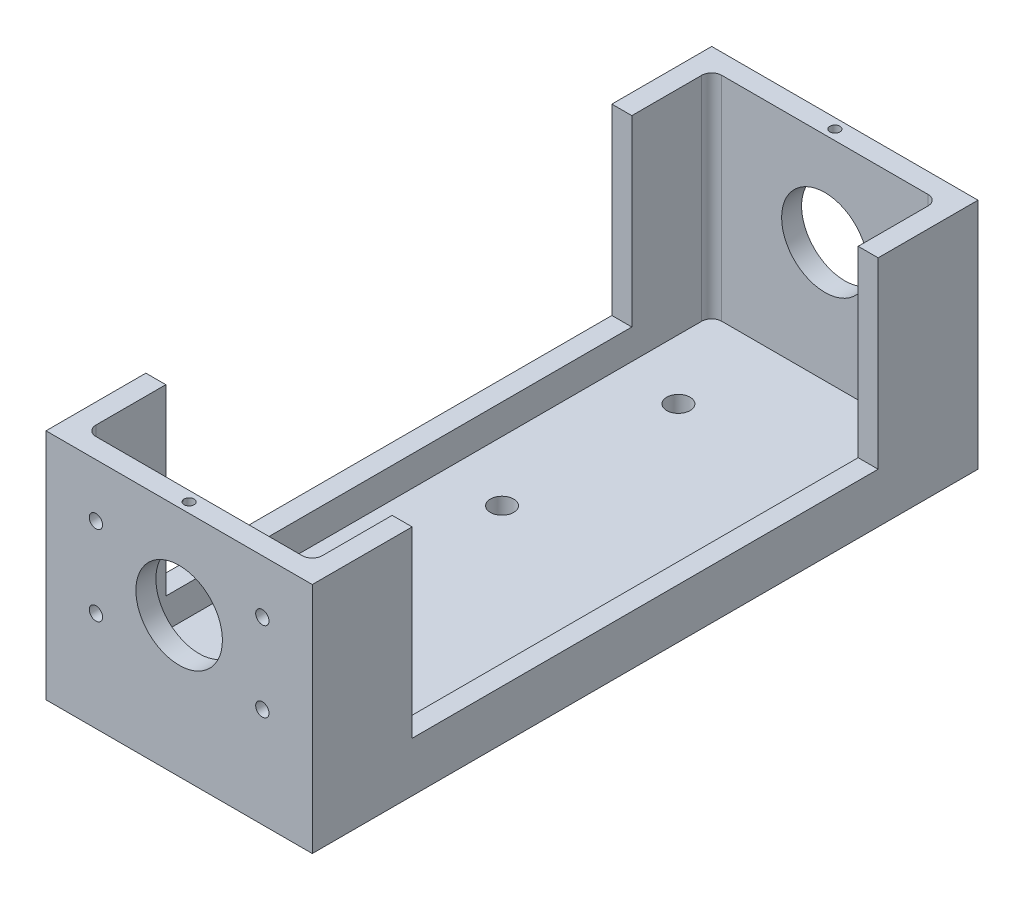
SolidWorks part; units mm, degrees
ref_plane "前视基准面" through (0, 0, 0) normal (0, 0, 1) x (1, 0, 0)
ref_plane "上视基准面" through (0, 0, 0) normal (0, 1, 0) x (1, 0, 0)
ref_plane "右视基准面" through (0, 0, 0) normal (1, 0, 0) x (0, 0, -1)
sketch "草图1" plane through (0, 0, 0) normal (0, 0, 1) x (1, 0, 0)
  line L1 (-40, -35) -> (40, -35)
  line L2 (-40, -35) -> (-40, 35)
  line L3 (-40, 35) -> (40, 35)
  line L4 (40, -35) -> (40, 35)
  line L5 (-40, -35) -> (40, 35) construction
  line L6 (-40, 35) -> (40, -35) construction
  point P0 (0, 0)
  dimension "D1" = 80
  dimension "D2" = 70
extrude "凸台-拉伸1" add sketch "草图1" against normal blind 200
sketch "草图2" plane through (0, 35, 0) normal (0, 1, 0) x (1, 0, 0)
  line L0 (-34, 191) -> (-34, 9)
  line L1 (-31, 6) -> (31, 6)
  line L2 (34, 9) -> (34, 191)
  line L3 (31, 194) -> (-31, 194)
  line L4 (-40, 0) -> (40, 0)
  line L5 (40, 0) -> (40, 200)
  line L6 (40, 200) -> (-40, 200)
  line L7 (-40, 200) -> (-40, 0)
  line L8 (-40, 0) -> (40, 0)
  line L9 (40, 0) -> (40, 200)
  line L10 (40, 200) -> (-40, 200)
  line L11 (-40, 200) -> (-40, 0)
  line L12 (-34, 6) -> (34, 6) construction
  line L13 (34, 6) -> (34, 194) construction
  line L14 (-34, 194) -> (-34, 6) construction
  line L15 (34, 194) -> (-34, 194) construction
  arc A0 (31, 6) -> (34, 9) centre (31, 9) ccw
  arc A1 (-34, 9) -> (-31, 6) centre (-31, 9) ccw
  arc A2 (34, 191) -> (31, 194) centre (31, 191) ccw
  arc A3 (-34, 191) -> (-31, 194) centre (-31, 191) cw
  dimension "D3" = 3
  dimension "D1" = 0
  dimension "D2" = 6
extrude "切除-拉伸1" cut sketch "草图2" against normal blind 64 contours A3 L0 A1 L1 A0 L2 A2 L3 region at (0, 35, -100)
sketch "草图3" plane through (0, 0, 0) normal (0, 0, 1) x (1, 0, 0)
  line L0 (0, 0) -> (0, 37.0041) construction
  line L1 (-40, -29) -> (40, -29) construction
  line L2 (-40, 35) -> (-40, -35) construction
  line L3 (40, -35) -> (40, 35) construction
  line L4 (-40, -35) -> (40, -35) construction
  line L5 (40, 35) -> (-40, 35) construction
  line L6 (-34, -29) -> (40, -29) construction
  line L9 (0, 7) -> (0, 35) construction
  line L10 (-26, 7) -> (26, 7) construction
  circle A0 centre (-26, 7) radius 3.5 construction
  circle A1 centre (0, 7) radius 13
  circle A2 centre (26, 7) radius 3.5 construction
  dimension "D2" = 7
  dimension "D3" = 26
  dimension "D4" = 7
  dimension "D1" = 6
  dimension "D5" = 28
  dimension "D6" = 26
  dimension "D7" = 26
extrude "切除-拉伸2" cut sketch "草图3" against normal through all
sketch "草图4" plane through (-40, 0, 0) normal (-1, 0, 0) x (0, 0, 1)
  line L0 (-126.5, -4) -> (-153.5, -4)
  line L1 (-126.5, -4) -> (-126.5, 32)
  line L2 (-126.5, 32) -> (-153.5, 32)
  line L3 (-153.5, -4) -> (-153.5, 32)
  line L4 (-140, -1.9135) -> (-140, 22.4271) construction
  line L5 (-200, 35) -> (0, 35) construction
  line L6 (-200, 35) -> (-200, -35) construction
  circle A0 centre (-121.5, 2) radius 2
  circle A1 centre (-121.5, 26) radius 2
  circle A2 centre (-158.5, 26) radius 2
  circle A3 centre (-158.5, 2) radius 2
  dimension "D1" = 4
  dimension "D2" = 4
  dimension "D3" = 36
  dimension "D4" = 6
  dimension "D5" = 5
  dimension "D6" = 6
  dimension "D7" = 5
  dimension "D8" = 27
  dimension "D9" = 3
  dimension "D10" = 60
extrude "切除-拉伸3" cut sketch "草图4" against normal blind 10
sketch "草图6" plane through (0, -29, 0) normal (0, 1, 0) x (1, 0, 0)
  line L0 (-16, 113) -> (-16, 166) construction
  line L1 (-16, 139.5) -> (-23.7867, 139.5) construction
  line L2 (-34, 191) -> (-34, 9) construction
  line L3 (31, 194) -> (-31, 194) construction
  circle A0 centre (-16, 166) radius 3.5
  circle A1 centre (-16, 113) radius 3.5
  dimension "D2" = 7
  dimension "D5" = 7
  dimension "D1" = 53
  dimension "D3" = 18
  dimension "D4" = 54.5
extrude "切除-拉伸5" cut sketch "草图6" against normal blind 10
sketch "草图7" plane through (0, 35, 0) normal (0, 1, 0) x (1, 0, 0)
  line L0 (0, -10.1016) -> (0, 210.5413) construction
  line L1 (40, 0) -> (-40, 0) construction
  line L2 (40, 200) -> (40, 0) construction
  line L3 (-40, 200) -> (-40, 0) construction
  line L4 (40, 200) -> (-40, 200) construction
  circle A0 centre (-37, 150) radius 1.5
  circle A1 centre (-37, 50) radius 1.5
  circle A2 centre (37, 50) radius 1.5
  circle A3 centre (37, 150) radius 1.5
  circle A4 centre (0, 197) radius 1.5
  circle A5 centre (0, 3) radius 1.5
  dimension "D1" = 100
  dimension "D3" = 50
  dimension "D5" = 3
  dimension "D6" = 3
  dimension "D7" = 3
  dimension "D8" = 3
  dimension "D9" = 3
  dimension "D10" = 3
  dimension "D11" = 3
  dimension "D12" = 3
  dimension "D14" = 3
  dimension "D15" = 3
  dimension "D16" = 3
  dimension "D2" = 100
  dimension "D4" = 50
  dimension "D13" = 3
extrude "切除-拉伸6" cut sketch "草图7" against normal blind 10
sketch "草图8" plane through (40, 0, 0) normal (1, 0, 0) x (0, 0, -1)
  line L0 (200, 35) -> (0, 35) construction
  line L1 (30, 35) -> (170, 35)
  line L2 (30, 35) -> (30, -20)
  line L3 (30, -20) -> (170, -20)
  line L4 (170, 35) -> (170, -20)
  line L5 (30, 35) -> (170, -20) construction
  line L6 (30, -20) -> (170, 35) construction
  line L7 (0, -35) -> (0, 35) construction
  dimension "D1" = 140
  dimension "D2" = 55
  dimension "D3" = 30
extrude "切除-拉伸7" cut sketch "草图8" against normal through all
sketch "草图9" plane through (0, 0, -6) normal (0, 0, -1) x (-1, 0, 0)
  circle A0 centre (-25, -5) radius 2 construction
  circle A1 centre (-25, 19) radius 2 construction
  circle A2 centre (25, 19) radius 2 construction
  circle A3 centre (25, -5) radius 2 construction
  circle A4 centre (-25, -5) radius 2
  circle A5 centre (-25, 19) radius 2
  circle A6 centre (25, 19) radius 2
  circle A7 centre (25, -5) radius 2
extrude "切除-拉伸8" cut sketch "草图9" against normal blind 6
